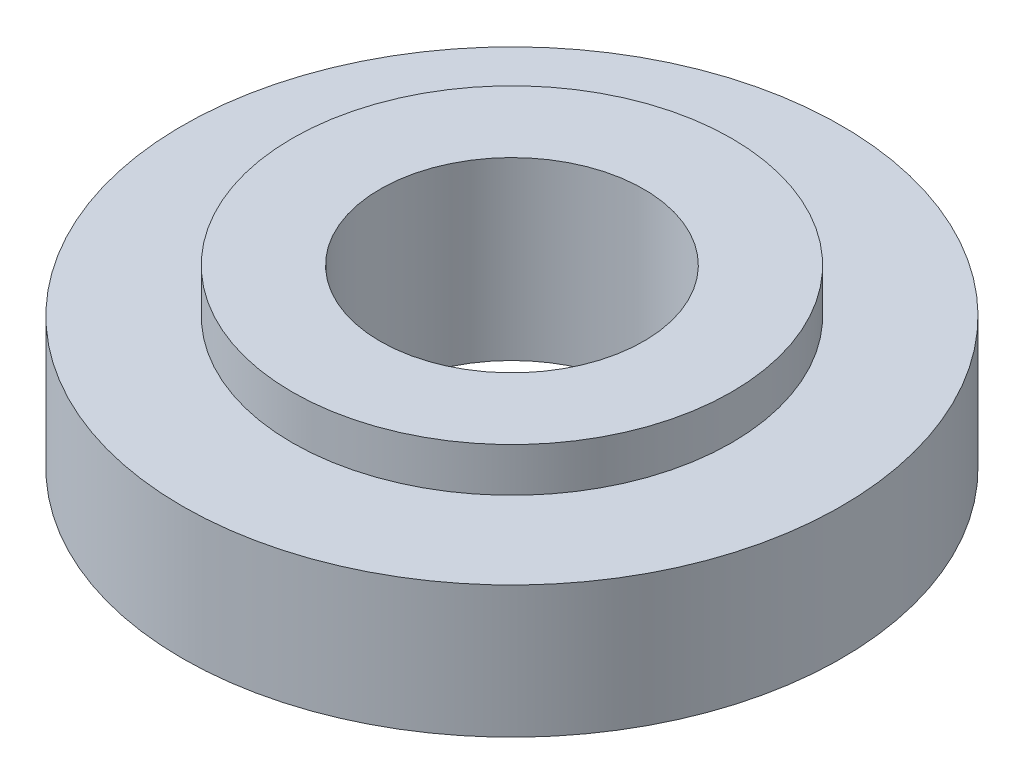
SolidWorks part; units mm, degrees
ref_plane "Front Plane" through (0, 0, 0) normal (0, 0, 1) x (1, 0, 0)
ref_plane "Top Plane" through (0, 0, 0) normal (0, 1, 0) x (1, 0, 0)
ref_plane "Right Plane" through (0, 0, 0) normal (1, 0, 0) x (0, 0, -1)
sketch "Sketch1" plane through (0, 0, 0) normal (0, 1, 0) x (1, 0, 0)
  circle A0 centre (0, 0) radius 3.75
  circle A1 centre (0, 0) radius 2.5
  circle A2 centre (0, 0) radius 1.5
  dimension "D1" = 7.5
  dimension "D2" = 5
  dimension "D3" = 3
extrude "Boss-Extrude1" add sketch "Sketch1" against normal blind 1.5 contours A0 A1 | A1 A2 region at (-3.6439, 0, 0) region at (-2.4293, 0, 0)
extrude "Boss-Extrude2" add sketch "Sketch1<3>" along normal blind 0.5 contours A1 A2 region at (-2.4293, 0, 0)
sketch "Sketch1<3>" plane through (0, 0, 0) normal (0, 1, 0) x (1, 0, 0) same geometry as "Sketch1"
